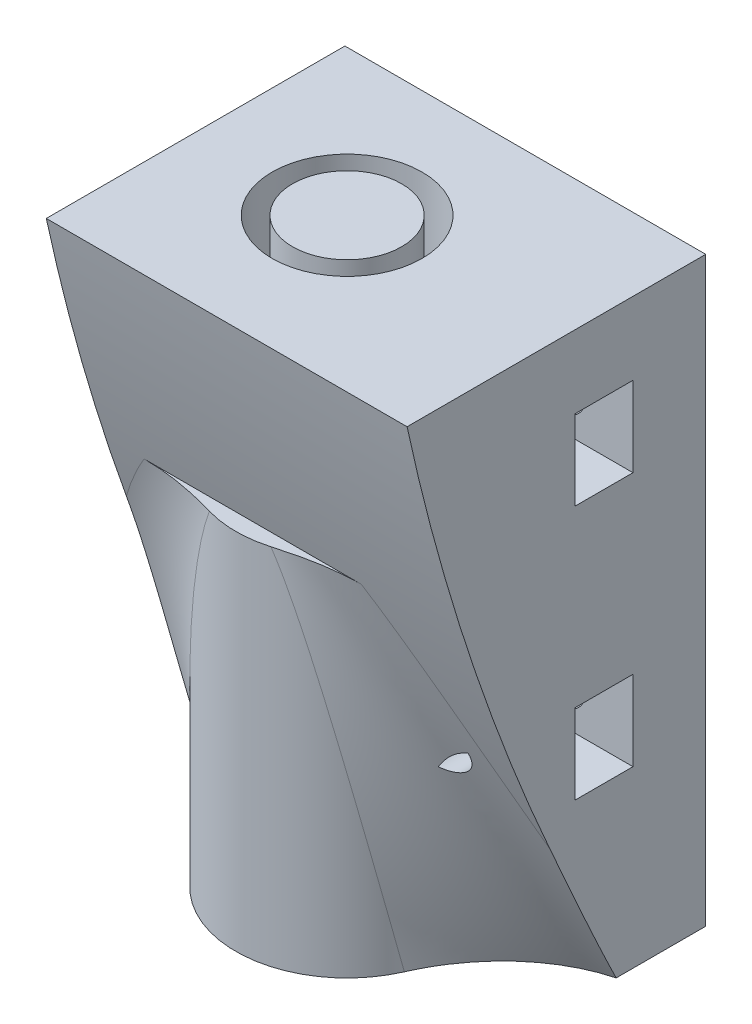
SolidWorks part; units mm, degrees
material "20% infill ABS"
ref_plane "Front" through (0, 0, 0) normal (0, 0, 1) x (1, 0, 0)
ref_plane "Top" through (0, 0, 0) normal (0, 1, 0) x (1, 0, 0)
ref_plane "Right" through (0, 0, 0) normal (1, 0, 0) x (0, 0, -1)
sketch "Sketch1" plane through (0, 0, 0) normal (0, 1, 0) x (1, 0, 0)
  line L1 (0, 0) -> (-24.8, 0)
  line L7 (-24.8, -32.15) -> (0, -32.15)
  line L8 (0, -32.15) -> (0, 0)
  line L11 (-24.8, 0) -> (-24.8, -32.15)
  line L12 (-24.8, -17.9) -> (-18.8, -17.9) construction
  line L13 (-18.8, -17.9) -> (-18.8, -16.65) construction
  line L14 (-18.8, -16.65) -> (-14.8, -16.65) construction
  line L15 (-14.8, -16.65) -> (-14.8, -22.15) construction
  line L16 (-14.8, -22.15) -> (-18.8, -22.15) construction
  line L17 (-18.8, -22.15) -> (-18.8, -20.9) construction
  line L18 (-18.8, -20.9) -> (-24.8, -20.9) construction
  line L19 (-6.25, 0) -> (-6.25, -6) construction
  line L20 (-6.25, -6) -> (-7.5, -6) construction
  line L21 (-7.5, -6) -> (-7.5, -10) construction
  line L22 (-7.5, -10) -> (-2, -10) construction
  line L23 (-2, -10) -> (-2, -6) construction
  line L24 (-2, -6) -> (-3.25, -6) construction
  line L25 (-3.25, -6) -> (-3.25, 0) construction
  circle A0 centre (-14.65, -10) radius 5.15 construction
  point P4 (-27.8, 0)
  dimension "D2" = 10.3
  dimension "D7" = 5
  dimension "D1" = 5.5
  dimension "D3" = 10
  dimension "D4" = 3
  dimension "D5" = 4
  dimension "D6" = 10
  dimension "D8" = 2
  dimension "D9" = 2
  dimension "D10" = 10
  dimension "D11" = 3
extrude "Boss-Extrude1" add sketch "Sketch1" along normal blind 40
sketch "Sketch3" plane through (0, 0, 0) normal (0, -1, 0) x (1, 0, 0)
  circle A0 centre (-14.65, 10) radius 5.15 construction
  circle A1 centre (-14.65, 10) radius 5.15
extrude "Cut-Extrude2" cut sketch "Sketch3" against normal blind 20
ref_plane "Plane1" through (0, 25, 0) normal (0, -1, 0) x (-1, 0, 0)
sketch "Sketch4" plane through (0, 25, 0) normal (0, -1, 0) x (-1, 0, 0)
  circle A0 centre (14.65, -10) radius 3.75
  circle A1 centre (14.65, -10) radius 5.15
  circle A2 centre (14.65, -10) radius 5.15
  dimension "D2" = 7.5
  dimension "D1" = 0
extrude "Cut-Extrude3" cut sketch "Sketch4" against normal blind 20
sketch "Sketch5" plane through (-24.8, 0, 0) normal (-1, 0, 0) x (0, 0, 1)
  line L0 (0, -10) -> (56.6705, -8.9029)
  line L1 (56.6705, -8.9029) -> (55.0946, 72.5)
  line L2 (55.0946, 72.5) -> (24, 72.5)
  arc A0 (0, -10) -> (24, 72.5) centre (-129.7969, 72.5) ccw construction
  arc A1 (0, -10) -> (24, 72.5) centre (-129.7969, 72.5) ccw
extrude "Cut-Extrude4" cut sketch "Sketch5" against normal blind 30
sketch "Sketch6" plane through (0, 25, 0) normal (0, 1, 0) x (1, 0, 0)
  circle A0 centre (-14.65, -10) radius 5.15 construction
  circle A1 centre (-14.65, -10) radius 5.15
  circle A2 centre (-14.65, -10) radius 7.65
  dimension "D1" = 2.5
extrude "Boss-Extrude2" add sketch "Sketch6" against normal up to surface (25 mm away) up to face at (-13.15, 0, 3.7281)
fillet "Fillet1" radius 10 2 edges at (-22.2965, 8.8921, 10.23) (-7.6175, 15.4093, 13.0111)
ref_plane "Plane2" through (0, 0, 5) normal (0, 0, -1) x (-1, 0, 0)
sketch "Sketch7" plane through (0, 0, 5) normal (0, 0, -1) x (-1, 0, 0)
  line L0 (19.8, 40) -> (9.5, 40) construction
  line L1 (19.8, 40) -> (9.5, 40)
  line L2 (0, 40) -> (24.8, 40) construction
  line L4 (3.2369, 29.5) -> (6.4123, 29.5)
  line L5 (6.4123, 29.5) -> (8, 32.25)
  line L6 (8, 32.25) -> (6.4123, 35)
  line L7 (6.4123, 35) -> (3.2369, 35)
  line L10 (3.2369, 12) -> (6.4123, 12)
  line L11 (6.4123, 12) -> (8, 14.75)
  line L12 (8, 14.75) -> (6.4123, 17.5)
  line L13 (6.4123, 17.5) -> (3.2369, 17.5)
  line L15 (0, 40) -> (0, 0) construction
  line L16 (3.2369, 35) -> (0, 35)
  line L17 (0, 35) -> (0, 29.5)
  line L18 (0, 29.5) -> (3.2369, 29.5)
  line L19 (3.2369, 17.5) -> (0, 17.5)
  line L20 (0, 17.5) -> (0, 12)
  line L21 (0, 12) -> (3.2369, 12)
  line L23 (3.2369, 17.5) -> (1.6491, 14.75) [skipped]
  line L24 (1.6491, 14.75) -> (3.2369, 12) [skipped]
  line L25 (3.2369, 35) -> (1.6491, 32.25) [skipped]
  line L26 (1.6491, 32.25) -> (3.2369, 29.5) [skipped]
  circle A0 centre (4.8246, 32.25) radius 2.75 construction
  circle A1 centre (4.8246, 14.75) radius 2.75 construction
  dimension "D1" = 5.5
  dimension "D2" = 5
  dimension "D3" = 12
  dimension "D4" = 8
extrude "Cut-Extrude5" cut sketch "Sketch7" against normal blind 4 contours L17 L18 L4 L5 L6 L7 L16 | L20 L21 L10 L11 L12 L13 L19 region at (-4.8246, 32.25, 5) region at (-1.2645, 32.25, 5) region at (-4.8246, 14.75, 5) region at (-1.2645, 14.75, 5)
sketch "Sketch9" plane through (0, 0, 0) normal (0, 0, -1) x (-1, 0, 0)
  circle A0 centre (4.8246, 32.25) radius 1.545
  circle A1 centre (4.8246, 14.75) radius 1.545
  dimension "D1" = 3.09
extrude "Cut-Extrude6" cut sketch "Sketch9" against normal blind 13
